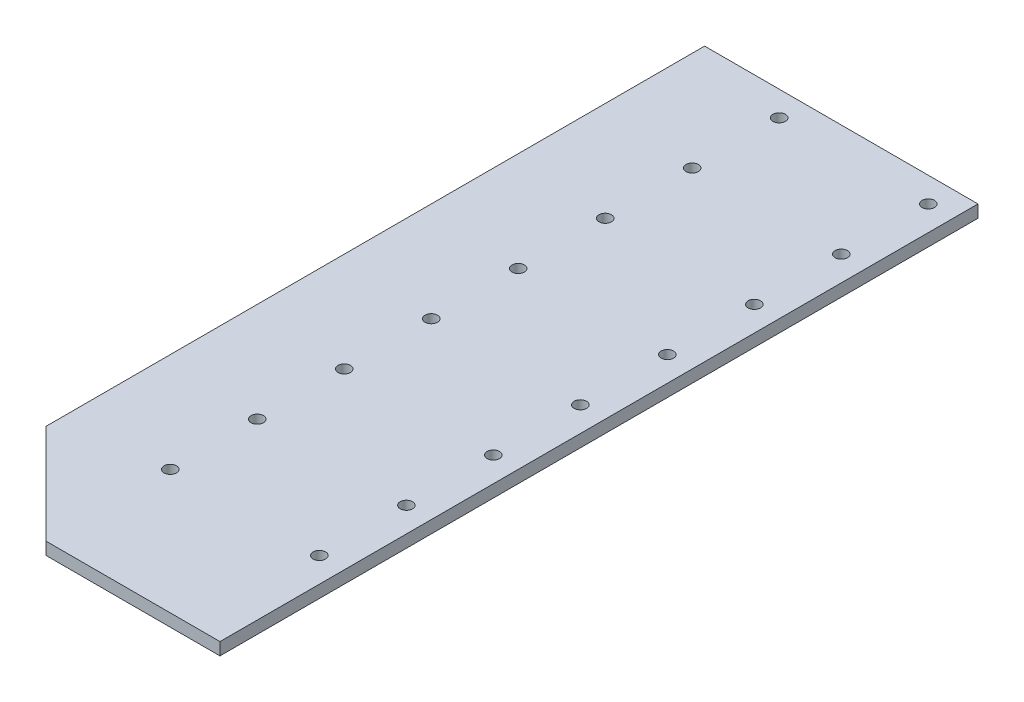
SolidWorks part; units mm, degrees
ref_plane "Front Plane" through (0, 0, 0) normal (0, 0, 1) x (1, 0, 0)
ref_plane "Top Plane" through (0, 0, 0) normal (0, 1, 0) x (1, 0, 0)
ref_plane "Right Plane" through (0, 0, 0) normal (1, 0, 0) x (0, 0, -1)
sketch "Sketch1" plane through (0, 0, 0) normal (0, 1, 0) x (1, 0, 0)
  line L0 (40, 301.9965) -> (40, -67.5183) construction
  line L2 (0, 0) -> (0, 265)
  line L3 (0, 265) -> (110, 265)
  line L4 (110, 0) -> (110, 265)
  line L7 (110, -40) -> (110, 0)
  line L8 (0, 0) -> (40, -40)
  line L9 (40, -40) -> (110, -40)
  circle A0 centre (40, 255) radius 2.5
  circle A1 centre (100, 255) radius 2.5
  circle A2 centre (40, 220) radius 2.5
  circle A3 centre (100, 220) radius 2.5
  circle A4 centre (40, 185) radius 2.5
  circle A5 centre (100, 185) radius 2.5
  circle A6 centre (40, 150) radius 2.5
  circle A7 centre (100, 150) radius 2.5
  circle A8 centre (40, 115) radius 2.5
  circle A9 centre (100, 115) radius 2.5
  circle A10 centre (40, 80) radius 2.5
  circle A11 centre (100, 80) radius 2.5
  circle A12 centre (40, 45) radius 2.5
  circle A13 centre (100, 45) radius 2.5
  circle A14 centre (40, 10) radius 2.5
  circle A15 centre (100, 10) radius 2.5
  dimension "D2" = 5
  dimension "D1" = 60
  dimension "D3" = 10
  dimension "D4" = 40
  dimension "D5" = 10
  dimension "D7" = 265
  dimension "D6" = 8
extrude "Boss-Extrude1" add sketch "Sketch1" along normal blind 5
